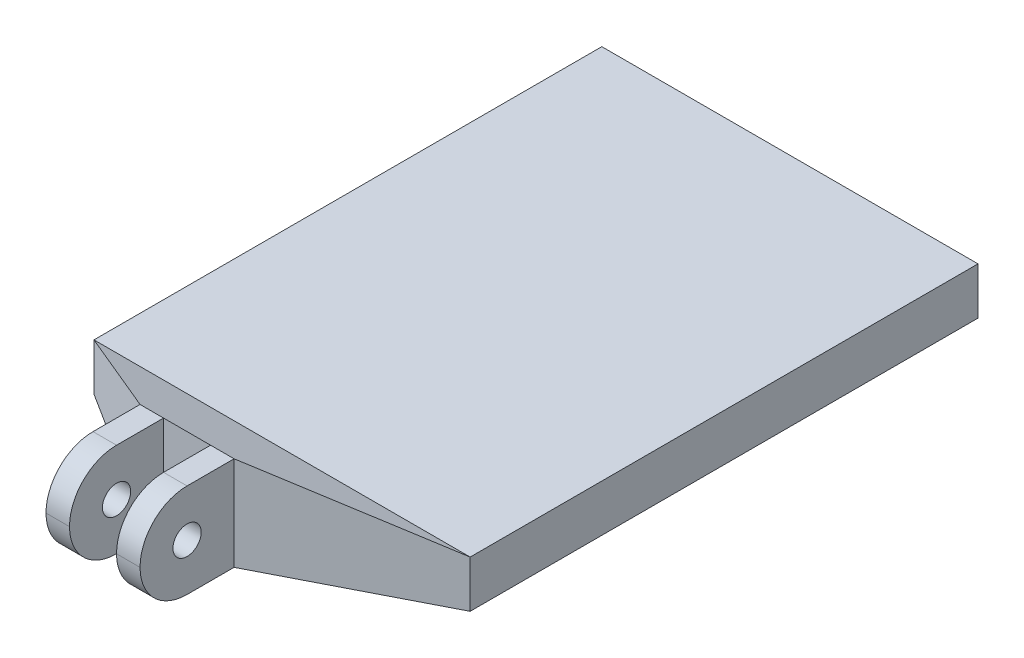
SolidWorks part; units mm, degrees
material "ABS"
ref_plane "Front Plane" through (0, 0, 0) normal (0, 0, 1) x (1, 0, 0)
ref_plane "Top Plane" through (0, 0, 0) normal (0, 1, 0) x (1, 0, 0)
ref_plane "Right Plane" through (0, 0, 0) normal (1, 0, 0) x (0, 0, -1)
sketch "Sketch1" plane through (0, 0, 0) normal (0, 0, 1) x (1, 0, 0)
  line L1 (-10, -1.25) -> (10, -1.25)
  line L2 (-10, -1.25) -> (-10, 1.25)
  line L3 (-10, 1.25) -> (10, 1.25)
  line L4 (10, -1.25) -> (10, 1.25)
  line L5 (-10, -1.25) -> (10, 1.25) construction
  line L6 (-10, 1.25) -> (10, -1.25) construction
  point P0 (0, 0)
  dimension "D1" = 2.5
  dimension "D2" = 20
extrude "Boss-Extrude1" add sketch "Sketch1" along normal blind 28
ref_plane "Plane1" through (0, 0, 31) normal (0, 0, 1) x (1, 0, 0)
sketch "Sketch3" plane through (0, 0, 31) normal (0, 0, 1) x (1, 0, 0)
  line L1 (-4.55, 2.5) -> (0.45, 2.5)
  line L2 (-4.55, 2.5) -> (-4.55, -2.5)
  line L3 (-4.55, -2.5) -> (0.45, -2.5)
  line L4 (0.45, 2.5) -> (0.45, -2.5)
  line L5 (-4.55, 2.5) -> (0.45, -2.5) construction
  line L6 (-4.55, -2.5) -> (0.45, 2.5) construction
  point P0 (-2.05, 0)
  dimension "D1" = 5
  dimension "D2" = 5
  dimension "D3" = 2.05
loft "Loft1" add profiles "Sketch3" section "Sketch3" section face at (0, 0, 28) connector at (0.45, 2.5, 31) connector at (10, 1.25, 28)
sketch "Sketch7" plane through (0, 0, 31) normal (0, 0, 1) x (1, 0, 0)
  line L0 (-4.55, -2.5) -> (0.45, -2.5) construction
  line L1 (-4.55, 2.5) -> (-3.3, 2.5)
  line L2 (-4.55, 2.5) -> (-4.55, -2.5)
  line L3 (-4.55, -2.5) -> (-3.3, -2.5)
  line L4 (-3.3, 2.5) -> (-3.3, -2.5)
  line L6 (0.45, 2.5) -> (-0.8, 2.5)
  line L7 (0.45, 2.5) -> (0.45, -2.5)
  line L8 (0.45, -2.5) -> (-0.8, -2.5)
  line L9 (-0.8, 2.5) -> (-0.8, -2.5)
  dimension "D1" = 2.5
extrude "Boss-Extrude3" add sketch "Sketch7" along normal blind 5
fillet "Fillet1" radius 2.5 4 edges at (-0.175, -2.5, 36) (-3.925, -2.5, 36) (-3.925, 2.5, 36) (-0.175, 2.5, 36)
sketch "Sketch8" plane through (0.45, 0, 0) normal (1, 0, 0) x (0, 0, -1)
  circle A0 centre (-33.5, 0) radius 0.75
  dimension "D1" = 1.5
extrude "Cut-Extrude3" cut sketch "Sketch8" against normal through all
chamfer "Chamfer1" distance 1 angle 45 4 edges at (0, 1.25, 0) (-10, 0, 0) (0, -1.25, 0) (10, 0, 0)
